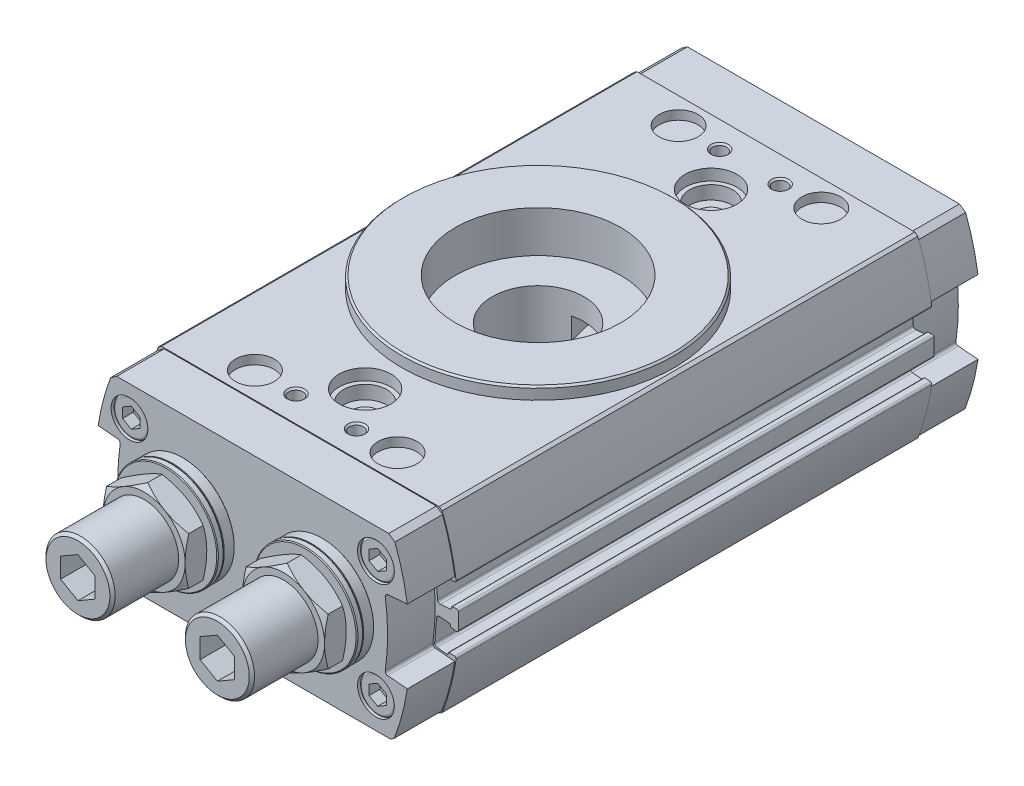
SolidWorks part; units mm, degrees
ref_plane "Front Plane" through (0, 0, 0) normal (0, 0, 1) x (1, 0, 0)
ref_plane "Top Plane" through (0, 0, 0) normal (0, 1, 0) x (1, 0, 0)
ref_plane "Right Plane" through (0, 0, 0) normal (1, 0, 0) x (0, 0, -1)
sketch "Sketch1" plane through (0, 0, 0) normal (0, 0, 1) x (1, 0, 0)
  line L0 (-32.8299, 0.5) -> (-32.1158, 0)
  line L1 (-32.1158, 0) -> (32.1158, 0)
  line L2 (32.1158, 0) -> (32.8299, 0.5)
  line L3 (32.8299, 40.9) -> (32.1158, 41.4)
  line L4 (32.1158, 41.4) -> (-32.1158, 41.4)
  line L5 (-32.1158, 41.4) -> (-32.8299, 40.9)
  arc A0 (-32.8299, 40.9) -> (-32.8299, 0.5) centre (19.4, 20.7) ccw
  arc A1 (32.8299, 0.5) -> (32.8299, 40.9) centre (-19.4, 20.7) ccw
extrude "Boss-Extrude1" add sketch "Sketch1" against normal blind 55 and the other way blind 55
sketch "Sketch2" plane through (0, 0, 0) normal (0, 0, 1) x (1, 0, 0)
  line L0 (31.6179, 12.9542) -> (33.9091, 12.7538)
  line L1 (34.2341, 13.0265) -> (34.2472, 13.1759)
  line L2 (34.4639, 13.3577) -> (35.6783, 13.2515)
  line L3 (36.0395, 12.7965) -> (41.6, 12.7965)
  line L4 (41.6, 12.7965) -> (41.6, 28.5837)
  line L5 (41.6, 28.5837) -> (36.0423, 28.5837)
  line L6 (35.6811, 28.1289) -> (34.6909, 28.0423)
  line L7 (34.4742, 28.2241) -> (34.4612, 28.3735)
  line L8 (34.1362, 28.6462) -> (31.8449, 28.4458)
  line L9 (31.2995, 27.7958) -> (31.7614, 22.5159)
  line L10 (32.4114, 21.9705) -> (34.7027, 22.171)
  line L11 (34.9754, 22.496) -> (34.9623, 22.6454)
  line L12 (35.1441, 22.8621) -> (36.1343, 22.9487)
  line L13 (36.1337, 18.4315) -> (34.9171, 18.5379)
  line L14 (34.7353, 18.7546) -> (34.7483, 18.904)
  line L15 (34.4756, 19.229) -> (32.1844, 19.4295)
  line L16 (31.5344, 18.8841) -> (31.0725, 13.6042)
  arc A0 (31.0725, 13.6042) -> (31.6179, 12.9542) centre (31.6702, 13.552) ccw
  arc A1 (33.9091, 12.7538) -> (34.2341, 13.0265) centre (33.9353, 13.0526) ccw
  arc A2 (34.2472, 13.1759) -> (34.4639, 13.3577) centre (34.4464, 13.1585) cw
  arc A3 (35.6783, 13.2515) -> (36.0395, 12.7965) centre (35.6435, 12.853) cw
  arc A4 (36.0423, 28.5837) -> (35.6811, 28.1289) centre (35.6463, 28.5274) cw
  arc A5 (34.6909, 28.0423) -> (34.4742, 28.2241) centre (34.6735, 28.2415) cw
  arc A6 (34.4612, 28.3735) -> (34.1362, 28.6462) centre (34.1623, 28.3474) ccw
  arc A7 (31.8449, 28.4458) -> (31.2995, 27.7958) centre (31.8972, 27.848) ccw
  arc A8 (31.7614, 22.5159) -> (32.4114, 21.9705) centre (32.3591, 22.5682) ccw
  arc A9 (34.7027, 22.171) -> (34.9754, 22.496) centre (34.6765, 22.4698) ccw
  arc A10 (34.9623, 22.6454) -> (35.1441, 22.8621) centre (35.1616, 22.6628) cw
  arc A11 (36.1343, 22.9487) -> (36.569, 22.5635) centre (36.1692, 22.5502) cw
  arc A12 (36.569, 22.5635) -> (36.5683, 18.8165) centre (-19.4, 20.7) cw
  arc A13 (36.5683, 18.8165) -> (36.1337, 18.4315) centre (36.1685, 18.83) cw
  arc A14 (34.9171, 18.5379) -> (34.7353, 18.7546) centre (34.9345, 18.7372) cw
  arc A15 (34.7483, 18.904) -> (34.4756, 19.229) centre (34.4495, 18.9302) ccw
  arc A16 (32.1844, 19.4295) -> (31.5344, 18.8841) centre (32.1321, 18.8318) ccw
extrude "Cut-Extrude1" cut sketch "Sketch2" along normal blind 55 and the other way blind 55
sketch "Sketch3" plane through (0, 0, 0) normal (0, 0, 1) x (1, 0, 0)
  line L0 (-41.6, 12.7965) -> (-36.0395, 12.7965)
  line L1 (-35.6783, 13.2515) -> (-34.4639, 13.3577)
  line L2 (-34.2472, 13.1759) -> (-34.2341, 13.0265)
  line L3 (-33.9091, 12.7538) -> (-31.6179, 12.9542)
  line L4 (-31.0725, 13.6042) -> (-31.5344, 18.8841)
  line L5 (-32.1844, 19.4295) -> (-34.4756, 19.229)
  line L6 (-34.7483, 18.904) -> (-34.7353, 18.7546)
  line L7 (-34.9171, 18.5379) -> (-36.1337, 18.4315)
  line L8 (-36.1343, 22.9487) -> (-35.1441, 22.8621)
  line L9 (-34.9623, 22.6454) -> (-34.9754, 22.496)
  line L10 (-34.7027, 22.171) -> (-32.4114, 21.9705)
  line L11 (-31.7614, 22.5159) -> (-31.2995, 27.7958)
  line L12 (-31.8449, 28.4458) -> (-34.1362, 28.6462)
  line L13 (-34.4612, 28.3735) -> (-34.4742, 28.2241)
  line L14 (-34.6909, 28.0423) -> (-35.6811, 28.1289)
  line L15 (-36.0423, 28.5837) -> (-41.6, 28.5837)
  line L16 (-41.6, 28.5837) -> (-41.6, 12.7965)
  arc A0 (-36.0395, 12.7965) -> (-35.6783, 13.2515) centre (-35.6435, 12.853) cw
  arc A1 (-34.4639, 13.3577) -> (-34.2472, 13.1759) centre (-34.4464, 13.1585) cw
  arc A2 (-34.2341, 13.0265) -> (-33.9091, 12.7538) centre (-33.9353, 13.0526) ccw
  arc A3 (-31.6179, 12.9542) -> (-31.0725, 13.6042) centre (-31.6702, 13.552) ccw
  arc A4 (-31.5344, 18.8841) -> (-32.1844, 19.4295) centre (-32.1321, 18.8318) ccw
  arc A5 (-34.4756, 19.229) -> (-34.7483, 18.904) centre (-34.4495, 18.9302) ccw
  arc A6 (-34.7353, 18.7546) -> (-34.9171, 18.5379) centre (-34.9345, 18.7372) cw
  arc A7 (-36.1337, 18.4315) -> (-36.5683, 18.8165) centre (-36.1685, 18.83) cw
  arc A8 (-36.5683, 18.8165) -> (-36.569, 22.5635) centre (19.4, 20.7) cw
  arc A9 (-36.569, 22.5635) -> (-36.1343, 22.9487) centre (-36.1692, 22.5502) cw
  arc A10 (-35.1441, 22.8621) -> (-34.9623, 22.6454) centre (-35.1616, 22.6628) cw
  arc A11 (-34.9754, 22.496) -> (-34.7027, 22.171) centre (-34.6765, 22.4698) ccw
  arc A12 (-32.4114, 21.9705) -> (-31.7614, 22.5159) centre (-32.3591, 22.5682) ccw
  arc A13 (-31.2995, 27.7958) -> (-31.8449, 28.4458) centre (-31.8972, 27.848) ccw
  arc A14 (-34.1362, 28.6462) -> (-34.4612, 28.3735) centre (-34.1623, 28.3474) ccw
  arc A15 (-34.4742, 28.2241) -> (-34.6909, 28.0423) centre (-34.6735, 28.2415) cw
  arc A16 (-35.6811, 28.1289) -> (-36.0423, 28.5837) centre (-35.6463, 28.5274) cw
extrude "Cut-Extrude2" cut sketch "Sketch3" along normal blind 55 and the other way blind 55
ref_plane "Plane1" through (0, 0, -55) normal (0, 0, 1) x (1, 0, 0)
sketch "Sketch4" plane through (0, 0, -55) normal (0, 0, 1) x (1, 0, 0)
  line L0 (-35.7512, 29.2) -> (-31.197, 28.8016)
  line L1 (-31.197, 12.5984) -> (-35.7512, 12.2)
  line L2 (-32.7449, 0.8) -> (-31.888, 0.2)
  line L3 (-31.888, 0.2) -> (31.888, 0.2)
  line L4 (31.888, 0.2) -> (32.7449, 0.8)
  line L5 (35.7512, 12.2) -> (31.197, 12.5984)
  line L6 (31.197, 28.8016) -> (35.7512, 29.2)
  line L7 (32.8953, 40.1997) -> (31.4668, 41.2)
  line L8 (31.4668, 41.2) -> (-31.4668, 41.2)
  line L9 (-31.4668, 41.2) -> (-32.8953, 40.1997)
  arc A0 (-31.197, 28.8016) -> (-30.6557, 28.1163) centre (-31.2493, 28.2038) cw
  arc A1 (-30.6557, 28.1163) -> (-30.6557, 13.2837) centre (19.6, 20.7) ccw
  arc A2 (-30.6557, 13.2837) -> (-31.197, 12.5984) centre (-31.2493, 13.1962) cw
  arc A3 (-35.7512, 12.2) -> (-32.7449, 0.8) centre (19.6, 20.7) ccw
  arc A4 (32.7449, 0.8) -> (35.7512, 12.2) centre (-19.6, 20.7) ccw
  arc A5 (31.197, 12.5984) -> (30.6557, 13.2837) centre (31.2493, 13.1962) cw
  arc A6 (30.6557, 13.2837) -> (30.6557, 28.1163) centre (-19.6, 20.7) ccw
  arc A7 (30.6557, 28.1163) -> (31.197, 28.8016) centre (31.2493, 28.2038) cw
  arc A8 (35.7512, 29.2) -> (32.8953, 40.1997) centre (-19.6, 20.7) ccw
  arc A9 (-32.8953, 40.1997) -> (-35.7512, 29.2) centre (19.6, 20.7) ccw
extrude "Boss-Extrude2" add sketch "Sketch4" against normal blind 11
ref_plane "Plane2" through (0, 0, 55) normal (0, 0, 1) x (1, 0, 0)
sketch "Sketch5" plane through (0, 0, 55) normal (0, 0, 1) x (1, 0, 0)
  line L0 (-35.7512, 29.2) -> (-31.197, 28.8016)
  line L1 (-31.197, 12.5984) -> (-35.7512, 12.2)
  line L2 (-32.7449, 0.8) -> (-31.888, 0.2)
  line L3 (-31.888, 0.2) -> (31.888, 0.2)
  line L4 (31.888, 0.2) -> (32.7449, 0.8)
  line L5 (35.7512, 12.2) -> (31.197, 12.5984)
  line L6 (31.197, 28.8016) -> (35.7512, 29.2)
  line L7 (32.8953, 40.1997) -> (31.4668, 41.2)
  line L8 (31.4668, 41.2) -> (-31.4668, 41.2)
  line L9 (-31.4668, 41.2) -> (-32.8953, 40.1997)
  arc A0 (-31.197, 28.8016) -> (-30.6557, 28.1163) centre (-31.2493, 28.2038) cw
  arc A1 (-30.6557, 28.1163) -> (-30.6557, 13.2837) centre (19.6, 20.7) ccw
  arc A2 (-30.6557, 13.2837) -> (-31.197, 12.5984) centre (-31.2493, 13.1962) cw
  arc A3 (-35.7512, 12.2) -> (-32.7449, 0.8) centre (19.6, 20.7) ccw
  arc A4 (32.7449, 0.8) -> (35.7512, 12.2) centre (-19.6, 20.7) ccw
  arc A5 (31.197, 12.5984) -> (30.6557, 13.2837) centre (31.2493, 13.1962) cw
  arc A6 (30.6557, 13.2837) -> (30.6557, 28.1163) centre (-19.6, 20.7) ccw
  arc A7 (30.6557, 28.1163) -> (31.197, 28.8016) centre (31.2493, 28.2038) cw
  arc A8 (35.7512, 29.2) -> (32.8953, 40.1997) centre (-19.6, 20.7) ccw
  arc A9 (-32.8953, 40.1997) -> (-35.7512, 29.2) centre (19.6, 20.7) ccw
extrude "Boss-Extrude3" add sketch "Sketch5" along normal blind 11
ref_plane "Plane3" through (0, 20.7, 0) normal (0, 1, 0) x (1, 0, 0)
sketch "Sketch6" plane through (0, 20.7, 0) normal (0, 1, 0) x (1, 0, 0)
  line L0 (10, 66) -> (12.5, 66)
  line L1 (12.5, 66) -> (12.067, 65.567)
  line L2 (12.067, 65.567) -> (12.067, 59)
  line L3 (12.067, 59) -> (10, 57.8066)
  line L4 (10, 57.8066) -> (10, 66)
  line L5 (10, 57.8066) -> (10, 66) construction
revolve "Cut-Revolve1" cut sketch "Sketch6" angle 360 about L5 reverse direction yes
cosmetic thread "Cosmetic Thread1" parameters "D1"=7, "D2"=5
sketch "Sketch7" plane through (0, 20.7, 0) normal (0, 1, 0) x (1, 0, 0)
  line L0 (-10, 66) -> (-7.5, 66)
  line L1 (-7.5, 66) -> (-7.933, 65.567)
  line L2 (-7.933, 65.567) -> (-7.933, 59)
  line L3 (-7.933, 59) -> (-10, 57.8066)
  line L4 (-10, 57.8066) -> (-10, 66)
  line L5 (-10, 57.8066) -> (-10, 66) construction
revolve "Cut-Revolve2" cut sketch "Sketch7" angle 360 about L5 reverse direction yes
cosmetic thread "Cosmetic Thread2" parameters "D1"=7, "D2"=5
ref_plane "Plane4" through (0, 20.7, 0) normal (0, 1, 0) x (1, 0, 0)
sketch "Sketch8" plane through (0, 0, 0) normal (0, 0, 1) x (1, 0, 0)
  line L0 (0, 44.2) -> (31.1, 44.2)
  line L1 (31.1, 44.2) -> (31.5, 43.8)
  line L2 (31.5, 43.8) -> (31.5, 41.4)
  line L3 (31.5, 41.4) -> (0, 41.4)
  line L4 (0, 41.4) -> (0, 44.2)
  line L5 (0, 41.4) -> (0, 44.2) construction
revolve "Revolve1" add sketch "Sketch8" angle 360 about L5 reverse direction yes
ref_plane "Plane5" through (0, 41.4, 0) normal (0, 1, 0) x (1, 0, 0)
ref_plane "Plane6" through (0, 0, 0) normal (0, 0, 1) x (1, 0, 0)
ref_plane "Plane7" through (0, 0, 0) normal (0, 0, 1) x (1, 0, 0)
ref_plane "Plane8" through (0, 41.1, 0) normal (0, 1, 0) x (1, 0, 0)
sketch "Sketch9" plane through (0, 0, 0) normal (0, 0, 1) x (1, 0, 0)
  line L0 (0, 44.7) -> (19.125, 44.7)
  line L1 (19.125, 44.7) -> (19.125, 34.6)
  line L2 (19.125, 34.6) -> (10.6, 34.6)
  line L3 (10.6, 34.6) -> (10.6, 9)
  line L4 (10.6, 9) -> (7.5, 9)
  line L5 (7.5, 9) -> (7.5, 1.4)
  line L6 (7.5, 1.4) -> (8.5, 1.4)
  line L7 (8.5, 1.4) -> (8.5, 0)
  line L8 (8.5, 0) -> (0, 0)
  line L9 (0, 0) -> (0, 44.7)
  line L10 (0, 0) -> (0, 44.7) construction
revolve "Cut-Revolve3" cut sketch "Sketch9" angle 360 about L10 reverse direction yes
sketch "Sketch10" plane through (0, 0, 0) normal (1, 0, 0) x (0, 0, -1)
  line L0 (40, 41.4) -> (46, 41.4)
  line L1 (46, 41.4) -> (46, 38.8)
  line L2 (46, 38.8) -> (45, 38.8)
  line L3 (45, 38.8) -> (45, 35.7)
  line L4 (45, 35.7) -> (43, 35.7)
  line L5 (43, 35.7) -> (42.4585, 35.1585)
  line L6 (42.4585, 35.1585) -> (42.4585, 3.1415)
  line L7 (42.4585, 3.1415) -> (43, 2.6)
  line L8 (43, 2.6) -> (46, 2.6)
  line L9 (46, 2.6) -> (46, 0)
  line L10 (46, 0) -> (40, 0)
  line L11 (40, 0) -> (40, 41.4)
  line L12 (40, 0) -> (40, 41.4) construction
revolve "Cut-Revolve4" cut sketch "Sketch10" angle 360 about L12 reverse direction yes
cosmetic thread "Cosmetic Thread3" parameters "D1"=33.1, "D2"=6
sketch "Sketch11" plane through (0, 0, 0) normal (1, 0, 0) x (0, 0, -1)
  line L0 (-40, 41.4) -> (-34, 41.4)
  line L1 (-34, 41.4) -> (-34, 38.8)
  line L2 (-34, 38.8) -> (-35, 38.8)
  line L3 (-35, 38.8) -> (-35, 35.7)
  line L4 (-35, 35.7) -> (-37, 35.7)
  line L5 (-37, 35.7) -> (-37.5415, 35.1585)
  line L6 (-37.5415, 35.1585) -> (-37.5415, 3.1415)
  line L7 (-37.5415, 3.1415) -> (-37, 2.6)
  line L8 (-37, 2.6) -> (-34, 2.6)
  line L9 (-34, 2.6) -> (-34, 0)
  line L10 (-34, 0) -> (-40, 0)
  line L11 (-40, 0) -> (-40, 41.4)
  line L12 (-40, 0) -> (-40, 41.4) construction
revolve "Cut-Revolve5" cut sketch "Sketch11" angle 360 about L12 reverse direction yes
cosmetic thread "Cosmetic Thread4" parameters "D1"=33.1, "D2"=6
ref_plane "Plane9" through (0, 0, 49) normal (0, 0, 1) x (1, 0, 0)
sketch "Sketch12" plane through (0, 0, 49) normal (0, 0, 1) x (1, 0, 0)
  line L0 (7, 41.4) -> (9, 41.4)
  line L1 (9, 41.4) -> (8.621, 41.021)
  line L2 (8.621, 41.021) -> (8.621, 32.9)
  line L3 (8.621, 32.9) -> (7, 31.9641)
  line L4 (7, 31.9641) -> (7, 41.4)
  line L5 (7, 31.9641) -> (7, 41.4) construction
revolve "Cut-Revolve6" cut sketch "Sketch12" angle 360 about L5 reverse direction yes
cosmetic thread "Cosmetic Thread5" parameters "D1"=7, "D2"=4
sketch "Sketch13" plane through (0, 0, 49) normal (0, 0, 1) x (1, 0, 0)
  line L0 (-7, 41.4) -> (-5, 41.4)
  line L1 (-5, 41.4) -> (-5.379, 41.021)
  line L2 (-5.379, 41.021) -> (-5.379, 32.9)
  line L3 (-5.379, 32.9) -> (-7, 31.9641)
  line L4 (-7, 31.9641) -> (-7, 41.4)
  line L5 (-7, 31.9641) -> (-7, 41.4) construction
revolve "Cut-Revolve7" cut sketch "Sketch13" angle 360 about L5 reverse direction yes
cosmetic thread "Cosmetic Thread6" parameters "D1"=7, "D2"=4
ref_plane "Plane10" through (0, 0, -49) normal (0, 0, 1) x (1, 0, 0)
sketch "Sketch14" plane through (0, 0, -49) normal (0, 0, 1) x (1, 0, 0)
  line L0 (7, 41.4) -> (9, 41.4)
  line L1 (9, 41.4) -> (8.621, 41.021)
  line L2 (8.621, 41.021) -> (8.621, 32.9)
  line L3 (8.621, 32.9) -> (7, 31.9641)
  line L4 (7, 31.9641) -> (7, 41.4)
  line L5 (7, 31.9641) -> (7, 41.4) construction
revolve "Cut-Revolve8" cut sketch "Sketch14" angle 360 about L5 reverse direction yes
cosmetic thread "Cosmetic Thread7" parameters "D1"=7, "D2"=4
sketch "Sketch15" plane through (0, 0, -49) normal (0, 0, 1) x (1, 0, 0)
  line L0 (-7, 41.4) -> (-5, 41.4)
  line L1 (-5, 41.4) -> (-5.379, 41.021)
  line L2 (-5.379, 41.021) -> (-5.379, 32.9)
  line L3 (-5.379, 32.9) -> (-7, 31.9641)
  line L4 (-7, 31.9641) -> (-7, 41.4)
  line L5 (-7, 31.9641) -> (-7, 41.4) construction
revolve "Cut-Revolve9" cut sketch "Sketch15" angle 360 about L5 reverse direction yes
cosmetic thread "Cosmetic Thread8" parameters "D1"=7, "D2"=4
ref_plane "Plane11" through (0, 0, 49) normal (0, 0, 1) x (1, 0, 0)
sketch "Sketch16" plane through (0, 0, 49) normal (0, 0, 1) x (1, 0, 0)
  line L0 (16.5, 41.4) -> (21, 41.4)
  line L1 (21, 41.4) -> (21, 39.3)
  line L2 (21, 39.3) -> (16.5, 39.3)
  line L3 (16.5, 39.3) -> (16.5, 41.4)
  line L4 (16.5, 39.3) -> (16.5, 41.4) construction
revolve "Cut-Revolve10" cut sketch "Sketch16" angle 360 about L4 reverse direction yes
sketch "Sketch17" plane through (0, 0, 49) normal (0, 0, 1) x (1, 0, 0)
  line L0 (-16.5, 41.4) -> (-12, 41.4)
  line L1 (-12, 41.4) -> (-12, 39.3)
  line L2 (-12, 39.3) -> (-16.5, 39.3)
  line L3 (-16.5, 39.3) -> (-16.5, 41.4)
  line L4 (-16.5, 39.3) -> (-16.5, 41.4) construction
revolve "Cut-Revolve11" cut sketch "Sketch17" angle 360 about L4 reverse direction yes
ref_plane "Plane12" through (0, 0, -49) normal (0, 0, 1) x (1, 0, 0)
sketch "Sketch18" plane through (0, 0, -49) normal (0, 0, 1) x (1, 0, 0)
  line L0 (16.5, 41.4) -> (21, 41.4)
  line L1 (21, 41.4) -> (21, 39.3)
  line L2 (21, 39.3) -> (16.5, 39.3)
  line L3 (16.5, 39.3) -> (16.5, 41.4)
  line L4 (16.5, 39.3) -> (16.5, 41.4) construction
revolve "Cut-Revolve12" cut sketch "Sketch18" angle 360 about L4 reverse direction yes
sketch "Sketch19" plane through (0, 0, -49) normal (0, 0, 1) x (1, 0, 0)
  line L0 (-16.5, 41.4) -> (-12, 41.4)
  line L1 (-12, 41.4) -> (-12, 39.3)
  line L2 (-12, 39.3) -> (-16.5, 39.3)
  line L3 (-16.5, 39.3) -> (-16.5, 41.4)
  line L4 (-16.5, 39.3) -> (-16.5, 41.4) construction
revolve "Cut-Revolve13" cut sketch "Sketch19" angle 360 about L4 reverse direction yes
ref_plane "Plane13" through (0, 7.2, 0) normal (0, 1, 0) x (1, 0, 0)
sketch "Sketch20" plane through (0, 7.2, 0) normal (0, 1, 0) x (1, 0, 0)
  line L0 (28.5, 66) -> (32.75, 66)
  line L1 (32.75, 66) -> (32.75, 65.1)
  line L2 (32.25, 65.6) -> (28.5, 65.6)
  line L3 (28.5, 65.6) -> (28.5, 66)
  line L4 (28.5, 65.6) -> (28.5, 66) construction
  arc A0 (32.75, 65.1) -> (32.25, 65.6) centre (32.25, 65.1) ccw
revolve "Cut-Revolve14" cut sketch "Sketch20" angle 360 about L4 reverse direction yes
sketch "Sketch21" plane through (0, 7.2, 0) normal (0, 1, 0) x (1, 0, 0)
  line L0 (-28.5, 66) -> (-24.25, 66)
  line L1 (-24.25, 66) -> (-24.25, 65.1)
  line L2 (-24.75, 65.6) -> (-28.5, 65.6)
  line L3 (-28.5, 65.6) -> (-28.5, 66)
  line L4 (-28.5, 65.6) -> (-28.5, 66) construction
  arc A0 (-24.25, 65.1) -> (-24.75, 65.6) centre (-24.75, 65.1) ccw
revolve "Cut-Revolve15" cut sketch "Sketch21" angle 360 about L4 reverse direction yes
sketch "Sketch22" plane through (0, 7.2, 0) normal (0, 1, 0) x (1, 0, 0)
  line L0 (28.5, -65.6) -> (32.25, -65.6)
  line L1 (32.75, -65.1) -> (32.75, -66)
  line L2 (32.75, -66) -> (28.5, -66)
  line L3 (28.5, -66) -> (28.5, -65.6)
  line L4 (28.5, -66) -> (28.5, -65.6) construction
  arc A0 (32.25, -65.6) -> (32.75, -65.1) centre (32.25, -65.1) ccw
revolve "Cut-Revolve16" cut sketch "Sketch22" angle 360 about L4 reverse direction yes
sketch "Sketch23" plane through (0, 7.2, 0) normal (0, 1, 0) x (1, 0, 0)
  line L0 (-28.5, -65.6) -> (-24.75, -65.6)
  line L1 (-24.25, -65.1) -> (-24.25, -66)
  line L2 (-24.25, -66) -> (-28.5, -66)
  line L3 (-28.5, -66) -> (-28.5, -65.6)
  line L4 (-28.5, -66) -> (-28.5, -65.6) construction
  arc A0 (-24.75, -65.6) -> (-24.25, -65.1) centre (-24.75, -65.1) ccw
revolve "Cut-Revolve17" cut sketch "Sketch23" angle 360 about L4 reverse direction yes
ref_plane "Plane14" through (0, 34.2, 0) normal (0, 1, 0) x (1, 0, 0)
sketch "Sketch24" plane through (0, 34.2, 0) normal (0, 1, 0) x (1, 0, 0)
  line L0 (28.5, 66) -> (32.75, 66)
  line L1 (32.75, 66) -> (32.75, 65.1)
  line L2 (32.25, 65.6) -> (28.5, 65.6)
  line L3 (28.5, 65.6) -> (28.5, 66)
  line L4 (28.5, 65.6) -> (28.5, 66) construction
  arc A0 (32.75, 65.1) -> (32.25, 65.6) centre (32.25, 65.1) ccw
revolve "Cut-Revolve18" cut sketch "Sketch24" angle 360 about L4 reverse direction yes
sketch "Sketch25" plane through (0, 34.2, 0) normal (0, 1, 0) x (1, 0, 0)
  line L0 (-28.5, 66) -> (-24.25, 66)
  line L1 (-24.25, 66) -> (-24.25, 65.1)
  line L2 (-24.75, 65.6) -> (-28.5, 65.6)
  line L3 (-28.5, 65.6) -> (-28.5, 66)
  line L4 (-28.5, 65.6) -> (-28.5, 66) construction
  arc A0 (-24.25, 65.1) -> (-24.75, 65.6) centre (-24.75, 65.1) ccw
revolve "Cut-Revolve19" cut sketch "Sketch25" angle 360 about L4 reverse direction yes
sketch "Sketch26" plane through (0, 34.2, 0) normal (0, 1, 0) x (1, 0, 0)
  line L0 (28.5, -65.6) -> (32.25, -65.6)
  line L1 (32.75, -65.1) -> (32.75, -66)
  line L2 (32.75, -66) -> (28.5, -66)
  line L3 (28.5, -66) -> (28.5, -65.6)
  line L4 (28.5, -66) -> (28.5, -65.6) construction
  arc A0 (32.25, -65.6) -> (32.75, -65.1) centre (32.25, -65.1) ccw
revolve "Cut-Revolve20" cut sketch "Sketch26" angle 360 about L4 reverse direction yes
sketch "Sketch27" plane through (0, 34.2, 0) normal (0, 1, 0) x (1, 0, 0)
  line L0 (-28.5, -65.6) -> (-24.75, -65.6)
  line L1 (-24.25, -65.1) -> (-24.25, -66)
  line L2 (-24.25, -66) -> (-28.5, -66)
  line L3 (-28.5, -66) -> (-28.5, -65.6)
  line L4 (-28.5, -66) -> (-28.5, -65.6) construction
  arc A0 (-24.75, -65.6) -> (-24.25, -65.1) centre (-24.75, -65.1) ccw
revolve "Cut-Revolve21" cut sketch "Sketch27" angle 360 about L4 reverse direction yes
ref_plane "Plane15" through (0, 0, 65.6) normal (0, 0, 1) x (1, 0, 0)
sketch "Sketch28" plane through (0, 0, 65.6) normal (0, 0, 1) x (1, 0, 0)
  line L0 (26.5, 33.0453) -> (28.5, 31.8906)
  line L1 (28.5, 31.8906) -> (30.5, 33.0453)
  line L2 (30.5, 33.0453) -> (30.5, 35.3547)
  line L3 (30.5, 35.3547) -> (28.5, 36.5094)
  line L4 (28.5, 36.5094) -> (26.5, 35.3547)
  line L5 (26.5, 35.3547) -> (26.5, 33.0453)
extrude "Cut-Extrude3" cut sketch "Sketch28" against normal blind 2.5
sketch "Sketch29" plane through (0, 0, 65.6) normal (0, 0, 1) x (1, 0, 0)
  line L0 (-30.5, 33.0453) -> (-28.5, 31.8906)
  line L1 (-28.5, 31.8906) -> (-26.5, 33.0453)
  line L2 (-26.5, 33.0453) -> (-26.5, 35.3547)
  line L3 (-26.5, 35.3547) -> (-28.5, 36.5094)
  line L4 (-28.5, 36.5094) -> (-30.5, 35.3547)
  line L5 (-30.5, 35.3547) -> (-30.5, 33.0453)
extrude "Cut-Extrude4" cut sketch "Sketch29" against normal blind 2.5
sketch "Sketch30" plane through (0, 0, 65.6) normal (0, 0, 1) x (1, 0, 0)
  line L0 (26.5, 6.0453) -> (28.5, 4.8906)
  line L1 (28.5, 4.8906) -> (30.5, 6.0453)
  line L2 (30.5, 6.0453) -> (30.5, 8.3547)
  line L3 (30.5, 8.3547) -> (28.5, 9.5094)
  line L4 (28.5, 9.5094) -> (26.5, 8.3547)
  line L5 (26.5, 8.3547) -> (26.5, 6.0453)
extrude "Cut-Extrude5" cut sketch "Sketch30" against normal blind 2.5
sketch "Sketch31" plane through (0, 0, 65.6) normal (0, 0, 1) x (1, 0, 0)
  line L0 (-30.5, 6.0453) -> (-28.5, 4.8906)
  line L1 (-28.5, 4.8906) -> (-26.5, 6.0453)
  line L2 (-26.5, 6.0453) -> (-26.5, 8.3547)
  line L3 (-26.5, 8.3547) -> (-28.5, 9.5094)
  line L4 (-28.5, 9.5094) -> (-30.5, 8.3547)
  line L5 (-30.5, 8.3547) -> (-30.5, 6.0453)
extrude "Cut-Extrude6" cut sketch "Sketch31" against normal blind 2.5
ref_plane "Plane16" through (0, 0, -65.6) normal (0, 0, 1) x (1, 0, 0)
sketch "Sketch32" plane through (0, 0, -65.6) normal (0, 0, 1) x (1, 0, 0)
  line L0 (26.5, 33.0453) -> (28.5, 31.8906)
  line L1 (28.5, 31.8906) -> (30.5, 33.0453)
  line L2 (30.5, 33.0453) -> (30.5, 35.3547)
  line L3 (30.5, 35.3547) -> (28.5, 36.5094)
  line L4 (28.5, 36.5094) -> (26.5, 35.3547)
  line L5 (26.5, 35.3547) -> (26.5, 33.0453)
extrude "Cut-Extrude7" cut sketch "Sketch32" along normal blind 2.5
sketch "Sketch33" plane through (0, 0, -65.6) normal (0, 0, 1) x (1, 0, 0)
  line L0 (-30.5, 33.0453) -> (-28.5, 31.8906)
  line L1 (-28.5, 31.8906) -> (-26.5, 33.0453)
  line L2 (-26.5, 33.0453) -> (-26.5, 35.3547)
  line L3 (-26.5, 35.3547) -> (-28.5, 36.5094)
  line L4 (-28.5, 36.5094) -> (-30.5, 35.3547)
  line L5 (-30.5, 35.3547) -> (-30.5, 33.0453)
extrude "Cut-Extrude8" cut sketch "Sketch33" along normal blind 2.5
sketch "Sketch34" plane through (0, 0, -65.6) normal (0, 0, 1) x (1, 0, 0)
  line L0 (26.5, 6.0453) -> (28.5, 4.8906)
  line L1 (28.5, 4.8906) -> (30.5, 6.0453)
  line L2 (30.5, 6.0453) -> (30.5, 8.3547)
  line L3 (30.5, 8.3547) -> (28.5, 9.5094)
  line L4 (28.5, 9.5094) -> (26.5, 8.3547)
  line L5 (26.5, 8.3547) -> (26.5, 6.0453)
extrude "Cut-Extrude9" cut sketch "Sketch34" along normal blind 2.5
sketch "Sketch35" plane through (0, 0, -65.6) normal (0, 0, 1) x (1, 0, 0)
  line L0 (-30.5, 6.0453) -> (-28.5, 4.8906)
  line L1 (-28.5, 4.8906) -> (-26.5, 6.0453)
  line L2 (-26.5, 6.0453) -> (-26.5, 8.3547)
  line L3 (-26.5, 8.3547) -> (-28.5, 9.5094)
  line L4 (-28.5, 9.5094) -> (-30.5, 8.3547)
  line L5 (-30.5, 8.3547) -> (-30.5, 6.0453)
extrude "Cut-Extrude10" cut sketch "Sketch35" along normal blind 2.5
sketch "Sketch36" plane through (0, 20.7, 0) normal (0, 1, 0) x (1, 0, 0)
  line L0 (16.125, -66) -> (27.975, -66)
  line L1 (27.975, -66) -> (28.075, -66.1)
  line L2 (28.075, -66.1) -> (28.075, -68.4)
  line L3 (28.075, -68.4) -> (27.975, -68.5)
  line L4 (27.975, -68.5) -> (16.125, -68.5)
  line L5 (16.125, -68.5) -> (16.125, -66)
  line L6 (16.125, -68.5) -> (16.125, -66) construction
revolve "Revolve2" add sketch "Sketch36" angle 360 about L6 reverse direction yes
sketch "Sketch37" plane through (0, 20.7, 0) normal (0, 1, 0) x (1, 0, 0)
  line L0 (-16.125, -66) -> (-4.275, -66)
  line L1 (-4.275, -66) -> (-4.175, -66.1)
  line L2 (-4.175, -66.1) -> (-4.175, -68.4)
  line L3 (-4.175, -68.4) -> (-4.275, -68.5)
  line L4 (-4.275, -68.5) -> (-16.125, -68.5)
  line L5 (-16.125, -68.5) -> (-16.125, -66)
  line L6 (-16.125, -68.5) -> (-16.125, -66) construction
revolve "Revolve3" add sketch "Sketch37" angle 360 about L6 reverse direction yes
sketch "Sketch38" plane through (0, 20.7, 0) normal (0, 1, 0) x (1, 0, 0)
  line L0 (16.125, -68.5) -> (27.925, -68.5)
  line L1 (27.925, -68.5) -> (28.125, -68.7)
  line L2 (28.125, -68.7) -> (28.125, -69.8)
  line L3 (28.125, -69.8) -> (27.925, -70)
  line L4 (27.925, -70) -> (16.125, -70)
  line L5 (16.125, -70) -> (16.125, -68.5)
  line L6 (16.125, -70) -> (16.125, -68.5) construction
revolve "Revolve4" add sketch "Sketch38" angle 360 about L6 reverse direction yes
sketch "Sketch39" plane through (0, 20.7, 0) normal (0, 1, 0) x (1, 0, 0)
  line L0 (-16.125, -68.5) -> (-4.3371, -68.5)
  line L1 (-4.3371, -68.5) -> (-4.125, -68.7121)
  line L2 (-4.125, -68.7121) -> (-4.125, -69.8232)
  line L3 (-4.125, -69.8232) -> (-4.3018, -70)
  line L4 (-4.3018, -70) -> (-16.125, -70)
  line L5 (-16.125, -70) -> (-16.125, -68.5)
  line L6 (-16.125, -70) -> (-16.125, -68.5) construction
revolve "Revolve5" add sketch "Sketch39" angle 360 about L6 reverse direction yes
ref_plane "Plane17" through (0, 0, 70) normal (0, 0, 1) x (1, 0, 0)
sketch "Sketch40" plane through (0, 0, 70) normal (0, 0, 1) x (1, 0, 0)
  line L0 (6.625, 15.2152) -> (16.125, 9.7303)
  line L1 (16.125, 9.7303) -> (25.625, 15.2152)
  line L2 (25.625, 15.2152) -> (25.625, 26.1848)
  line L3 (25.625, 26.1848) -> (16.125, 31.6697)
  line L4 (16.125, 31.6697) -> (6.625, 26.1848)
  line L5 (6.625, 26.1848) -> (6.625, 15.2152)
extrude "Boss-Extrude4" add sketch "Sketch40" along normal blind 5
sketch "Sketch41" plane through (0, 20.7, 0) normal (0, 1, 0) x (1, 0, 0)
  line L0 (25.625, -70) -> (28.075, -71.4145)
  line L1 (28.075, -71.4145) -> (28.075, -73.5855)
  line L2 (28.075, -73.5855) -> (25.625, -75)
  line L3 (25.625, -75) -> (29.075, -75)
  line L4 (29.075, -75) -> (29.075, -70)
  line L5 (29.075, -70) -> (25.625, -70)
  line L6 (16.125, -75) -> (16.125, -70) construction
revolve "Cut-Revolve22" cut sketch "Sketch41" angle 360 about L6 reverse direction yes
sketch "Sketch42" plane through (0, 0, 70) normal (0, 0, 1) x (1, 0, 0)
  line L0 (-25.625, 15.2152) -> (-16.125, 9.7303)
  line L1 (-16.125, 9.7303) -> (-6.625, 15.2152)
  line L2 (-6.625, 15.2152) -> (-6.625, 26.1848)
  line L3 (-6.625, 26.1848) -> (-16.125, 31.6697)
  line L4 (-16.125, 31.6697) -> (-25.625, 26.1848)
  line L5 (-25.625, 26.1848) -> (-25.625, 15.2152)
extrude "Boss-Extrude5" add sketch "Sketch42" along normal blind 5
sketch "Sketch43" plane through (0, 20.7, 0) normal (0, 1, 0) x (1, 0, 0)
  line L0 (-6.625, -75) -> (-3.175, -75)
  line L1 (-3.175, -75) -> (-3.175, -70)
  line L2 (-3.175, -70) -> (-6.625, -70)
  line L3 (-6.625, -70) -> (-4.175, -71.4145)
  line L4 (-4.175, -71.4145) -> (-4.175, -73.5855)
  line L5 (-4.175, -73.5855) -> (-6.625, -75)
  line L6 (-16.125, -75) -> (-16.125, -70) construction
revolve "Cut-Revolve23" cut sketch "Sketch43" angle 360 about L6 reverse direction yes
sketch "Sketch44" plane through (0, 20.7, 0) normal (0, 1, 0) x (1, 0, 0)
  line L0 (16.125, -75) -> (24.125, -75)
  line L1 (24.125, -75) -> (24.125, -89.6865)
  line L2 (24.125, -89.6865) -> (23.5115, -90.3)
  line L3 (23.5115, -90.3) -> (16.125, -90.3)
  line L4 (16.125, -90.3) -> (16.125, -75)
  line L5 (16.125, -90.3) -> (16.125, -75) construction
revolve "Revolve6" add sketch "Sketch44" angle 360 about L5 reverse direction yes
cosmetic thread "Cosmetic Thread9" parameters "D1"=15.3, "D2"=14.773
sketch "Sketch45" plane through (0, 20.7, 0) normal (0, 1, 0) x (1, 0, 0)
  line L0 (-16.125, -75) -> (-8.125, -75)
  line L1 (-8.125, -75) -> (-8.125, -89.6865)
  line L2 (-8.125, -89.6865) -> (-8.7385, -90.3)
  line L3 (-8.7385, -90.3) -> (-16.125, -90.3)
  line L4 (-16.125, -90.3) -> (-16.125, -75)
  line L5 (-16.125, -90.3) -> (-16.125, -75) construction
revolve "Revolve7" add sketch "Sketch45" angle 360 about L5 reverse direction yes
cosmetic thread "Cosmetic Thread10" parameters "D1"=15.3, "D2"=14.773
ref_plane "Plane18" through (0, 0, 129) normal (0, 0, 1) x (1, 0, 0)
ref_plane "Plane19" through (0, 0, 90.3) normal (0, 0, 1) x (1, 0, 0)
sketch "Sketch46" plane through (0, 0, 90.3) normal (0, 0, 1) x (1, 0, 0)
  line L0 (12.125, 18.3906) -> (16.125, 16.0812)
  line L1 (16.125, 16.0812) -> (20.125, 18.3906)
  line L2 (20.125, 18.3906) -> (20.125, 23.0094)
  line L3 (20.125, 23.0094) -> (16.125, 25.3188)
  line L4 (16.125, 25.3188) -> (12.125, 23.0094)
  line L5 (12.125, 23.0094) -> (12.125, 18.3906)
extrude "Cut-Extrude11" cut sketch "Sketch46" against normal blind 6
sketch "Sketch47" plane through (0, 0, 90.3) normal (0, 0, 1) x (1, 0, 0)
  line L0 (-20.125, 18.3906) -> (-16.125, 16.0812)
  line L1 (-16.125, 16.0812) -> (-12.125, 18.3906)
  line L2 (-12.125, 18.3906) -> (-12.125, 23.0094)
  line L3 (-12.125, 23.0094) -> (-16.125, 25.3188)
  line L4 (-16.125, 25.3188) -> (-20.125, 23.0094)
  line L5 (-20.125, 23.0094) -> (-20.125, 18.3906)
extrude "Cut-Extrude12" cut sketch "Sketch47" against normal blind 6
sketch "Sketch48" plane through (0, 0, 0) normal (1, 0, 0) x (0, 0, -1)
  line L0 (27.5, 0.4) -> (30.5, 0.4)
  line L1 (31, 0.9) -> (31, 4.4)
  line L2 (31, 4.4) -> (31.5, 4.4)
  line L3 (31.5, 4.4) -> (31.5, 2.1)
  line L4 (31.5, 2.1) -> (32, 2.1)
  line L5 (32, 2.1) -> (32, 0)
  line L6 (32, 0) -> (27.5, 0)
  line L7 (27.5, 0) -> (27.5, 0.4)
  line L8 (27.5, 0) -> (27.5, 0.4) construction
  arc A0 (30.5, 0.4) -> (31, 0.9) centre (30.5, 0.9) ccw
revolve "Cut-Revolve24" cut sketch "Sketch48" angle 360 about L8 reverse direction yes
sketch "Sketch49" plane through (0, 0, 0) normal (1, 0, 0) x (0, 0, -1)
  line L0 (-27.5, 0.4) -> (-24.5, 0.4)
  line L1 (-24, 0.9) -> (-24, 4.4)
  line L2 (-24, 4.4) -> (-23.5, 4.4)
  line L3 (-23.5, 4.4) -> (-23.5, 2.1)
  line L4 (-23.5, 2.1) -> (-23, 2.1)
  line L5 (-23, 2.1) -> (-23, 0)
  line L6 (-23, 0) -> (-27.5, 0)
  line L7 (-27.5, 0) -> (-27.5, 0.4)
  line L8 (-27.5, 0) -> (-27.5, 0.4) construction
  arc A0 (-24.5, 0.4) -> (-24, 0.9) centre (-24.5, 0.9) ccw
revolve "Cut-Revolve25" cut sketch "Sketch49" angle 360 about L8 reverse direction yes
ref_plane "Plane20" through (0, 0.4, 0) normal (0, 1, 0) x (1, 0, 0)
sketch "Sketch50" plane through (0, 0.4, 0) normal (0, 1, 0) x (1, 0, 0)
  line L0 (-1.5, 26.634) -> (0, 25.7679)
  line L1 (0, 25.7679) -> (1.5, 26.634)
  line L2 (1.5, 26.634) -> (1.5, 28.366)
  line L3 (1.5, 28.366) -> (0, 29.2321)
  line L4 (0, 29.2321) -> (-1.5, 28.366)
  line L5 (-1.5, 28.366) -> (-1.5, 26.634)
extrude "Cut-Extrude13" cut sketch "Sketch50" along normal blind 2
sketch "Sketch51" plane through (0, 0.4, 0) normal (0, 1, 0) x (1, 0, 0)
  line L0 (-1.5, -28.366) -> (0, -29.2321)
  line L1 (0, -29.2321) -> (1.5, -28.366)
  line L2 (1.5, -28.366) -> (1.5, -26.634)
  line L3 (1.5, -26.634) -> (0, -25.7679)
  line L4 (0, -25.7679) -> (-1.5, -26.634)
  line L5 (-1.5, -26.634) -> (-1.5, -28.366)
extrude "Cut-Extrude14" cut sketch "Sketch51" along normal blind 2
ref_plane "Plane21" through (0, 0, -55) normal (0, 0, 1) x (1, 0, 0)
ref_plane "Plane22" through (0, 20.7, 0) normal (0, 1, 0) x (1, 0, 0)
ref_plane "Plane23" through (0, 4.8, 0) normal (0, 1, 0) x (1, 0, 0)
ref_plane "Plane24" through (0, 30.7, 0) normal (0, 1, 0) x (1, 0, 0)
ref_plane "Plane25" through (0, 34.6, 0) normal (0, 1, 0) x (1, 0, 0)
ref_plane "Plane26" through (0, 30.6, 0) normal (0, 1, 0) x (1, 0, 0)
ref_plane "Plane27" through (0, 0, 0) normal (0.9703, 0, -0.2419) x (-0.2419, 0, -0.9703)
sketch "Sketch52" plane through (0, 0, 0) normal (0.9703, 0, -0.2419) x (-0.2419, 0, -0.9703)
  line L0 (0, 29.6) -> (17.125, 29.6)
  line L1 (17.125, 29.6) -> (17.125, 24.6)
  line L2 (17.125, 24.6) -> (0, 24.6)
  line L3 (0, 24.6) -> (0, 29.6)
  line L4 (0, 24.6) -> (0, 29.6) construction
revolve "Cut-Revolve26" cut sketch "Sketch52" angle 208 about L4 reverse direction yes
ref_plane "Plane28" through (0, 0, -66) normal (0, 0, 1) x (1, 0, 0)
ref_plane "Plane29" through (0, 0, 55) normal (0, 0, 1) x (1, 0, 0)
ref_plane "Plane30" through (0, 0, 66) normal (0, 0, 1) x (1, 0, 0)
ref_plane "Plane31" through (0, 0, 55) normal (0, 0, 1) x (1, 0, 0)
ref_plane "Plane32" through (0, 0, -55) normal (0, 0, 1) x (1, 0, 0)
ref_plane "Plane33" through (0, 0, -66) normal (0, 0, 1) x (1, 0, 0)
ref_plane "Plane34" through (0, 41.4, 0) normal (0, 1, 0) x (1, 0, 0)
ref_plane "Plane35" through (0, 0, 0) normal (1, 0, 0) x (0, 0, -1)
ref_plane "Plane36" through (0, 2.6, 0) normal (0, 1, 0) x (1, 0, 0)
ref_plane "ANBAU XY" through (0, 0, 0) normal (0, 1, 0) x (1, 0, 0)
ref_plane "ANBAU XZ" through (0, 0, 0) normal (0, 0, 1) x (1, 0, 0)
ref_plane "ANBAU YZ" through (0, 0, 0) normal (1, 0, 0) x (0, 0, -1)
ref_axis "ANBAU X" through (-80.9, 0, 0) along (1, 0, 0)
ref_axis "ANBAU Y" through (0, 0, 50) along (0, 0, -1)
ref_axis "ANBAU Z" through (0, 50, 0) along (0, -1, 0)
sketch3d "ANBAU"
  point P0 (0, 0, 0)
ref_plane "DASIQ11 XY" through (0, 0, 0) normal (0, 0, -1) x (-1, 0, 0)
ref_plane "DASIQ11 XZ" through (0, 41.8, 0) normal (0, 1, 0) x (1, 0, 0)
ref_plane "DASIQ11 YZ" through (0, 0, 0) normal (1, 0, 0) x (0, 0, -1)
ref_axis "DASIQ11 X" through (-80.9, 41.8, 0) along (1, 0, 0)
ref_axis "DASIQ11 Y" through (0, 50, 0) along (0, -1, 0)
ref_axis "DASIQ11 Z" through (0, 41.8, -80.9) along (0, 0, 1)
sketch3d "DASIQ11"
  point P0 (0, 41.8, 0)
ref_plane "FDT_QS1 XY" through (0, 0, -66) normal (0, 0, -1) x (-1, 0, 0)
ref_plane "FDT_QS1 XZ" through (0, 20.7, 0) normal (0, 1, 0) x (1, 0, 0)
ref_plane "FDT_QS1 YZ" through (10, 0, 0) normal (1, 0, 0) x (0, 0, -1)
ref_axis "FDT_QS1 X" through (-80.9, 20.7, -66) along (1, 0, 0)
ref_axis "FDT_QS1 Y" through (10, 50, -66) along (0, -1, 0)
ref_axis "FDT_QS1 Z" through (10, 20.7, -80.9) along (0, 0, 1)
sketch3d "FDT_QS1"
  point P0 (10, 20.7, -66)
ref_plane "FDT_QS2 XY" through (0, 0, -66) normal (0, 0, -1) x (-1, 0, 0)
ref_plane "FDT_QS2 XZ" through (0, 20.7, 0) normal (0, 1, 0) x (1, 0, 0)
ref_plane "FDT_QS2 YZ" through (-10, 0, 0) normal (1, 0, 0) x (0, 0, -1)
ref_axis "FDT_QS2 X" through (-80.9, 20.7, -66) along (1, 0, 0)
ref_axis "FDT_QS2 Y" through (-10, 50, -66) along (0, -1, 0)
ref_axis "FDT_QS2 Z" through (-10, 20.7, -80.9) along (0, 0, 1)
sketch3d "FDT_QS2"
  point P0 (-10, 20.7, -66)
ref_plane "FDT_SMX_LEFT_DOWN XY" through (-29.8806, -2.6142, 0) normal (-0.9962, -0.0872, 0) x (0, 0, 1)
ref_plane "FDT_SMX_LEFT_DOWN XZ" through (0, 0, 0) normal (0, 0, 1) x (1, 0, 0)
ref_plane "FDT_SMX_LEFT_DOWN YZ" through (-1.6499, 18.8584, 0) normal (-0.0872, 0.9962, 0) x (0.9962, 0.0872, 0)
ref_axis "FDT_SMX_LEFT_DOWN X" through (-25.5228, -52.4239, 0) along (-0.0872, 0.9962, 0)
ref_axis "FDT_SMX_LEFT_DOWN Y" through (-31.5305, 16.2442, 80.9) along (0, 0, -1)
ref_axis "FDT_SMX_LEFT_DOWN Z" through (-82.242, 11.8075, 0) along (0.9962, 0.0872, 0)
sketch3d "FDT_SMX_LEFT_DOWN"
  point P0 (-31.5305, 16.2442, 0)
ref_plane "FDT_SMX_LEFT_UP XY" through (-33.4751, 2.9287, 0) normal (-0.9962, 0.0872, 0) x (0, 0, 1)
ref_plane "FDT_SMX_LEFT_UP XZ" through (0, 0, 0) normal (0, 0, 1) x (1, 0, 0)
ref_plane "FDT_SMX_LEFT_UP YZ" through (1.9446, 22.2271, 0) normal (0.0872, 0.9962, 0) x (0.9962, -0.0872, 0)
ref_axis "FDT_SMX_LEFT_UP X" through (-37.8329, -46.881, 0) along (0.0872, 0.9962, 0)
ref_axis "FDT_SMX_LEFT_UP Y" through (-31.5305, 25.1558, 80.9) along (0, 0, -1)
ref_axis "FDT_SMX_LEFT_UP Z" through (-78.6475, 29.278, 0) along (0.9962, -0.0872, 0)
sketch3d "FDT_SMX_LEFT_UP"
  point P0 (-31.5305, 25.1558, 0)
ref_plane "FDT_SMX_RIGHT_DOWN XY" through (29.8806, -2.6142, 0) normal (0.9962, -0.0872, 0) x (0, 0, -1)
ref_plane "FDT_SMX_RIGHT_DOWN XZ" through (0, 0, 0) normal (0, 0, 1) x (1, 0, 0)
ref_plane "FDT_SMX_RIGHT_DOWN YZ" through (1.6499, 18.8584, 0) normal (-0.0872, -0.9962, 0) x (-0.9962, 0.0872, 0)
ref_axis "FDT_SMX_RIGHT_DOWN X" through (34.2383, 47.1955, 0) along (-0.0872, -0.9962, 0)
ref_axis "FDT_SMX_RIGHT_DOWN Y" through (31.5305, 16.2442, 80.9) along (0, 0, -1)
ref_axis "FDT_SMX_RIGHT_DOWN Z" through (82.242, 11.8075, 0) along (-0.9962, 0.0872, 0)
sketch3d "FDT_SMX_RIGHT_DOWN"
  point P0 (31.5305, 16.2442, 0)
ref_plane "FDT_SMX_RIGHT_UP XY" through (33.4751, 2.9287, 0) normal (0.9962, 0.0872, 0) x (0, 0, -1)
ref_plane "FDT_SMX_RIGHT_UP XZ" through (0, 0, 0) normal (0, 0, 1) x (1, 0, 0)
ref_plane "FDT_SMX_RIGHT_UP YZ" through (-1.9446, 22.2271, 0) normal (0.0872, -0.9962, 0) x (-0.9962, -0.0872, 0)
ref_axis "FDT_SMX_RIGHT_UP X" through (29.1173, 52.7384, 0) along (0.0872, -0.9962, 0)
ref_axis "FDT_SMX_RIGHT_UP Y" through (31.5305, 25.1558, 80.9) along (0, 0, -1)
ref_axis "FDT_SMX_RIGHT_UP Z" through (78.6475, 29.278, 0) along (-0.9962, -0.0872, 0)
sketch3d "FDT_SMX_RIGHT_UP"
  point P0 (31.5305, 25.1558, 0)
ref_plane "SLEEVE 1 XY" through (0, 2.6, 0) normal (0, 1, 0) x (1, 0, 0)
ref_plane "SLEEVE 1 XZ" through (0, 0, -40) normal (0, 0, 1) x (1, 0, 0)
ref_plane "SLEEVE 1 YZ" through (0, 0, 0) normal (1, 0, 0) x (0, 0, -1)
ref_axis "SLEEVE 1 X" through (-80.9, 2.6, -40) along (1, 0, 0)
ref_axis "SLEEVE 1 Y" through (0, 2.6, 50) along (0, 0, -1)
ref_axis "SLEEVE 1 Z" through (0, 50, -40) along (0, -1, 0)
sketch3d "SLEEVE 1"
  point P0 (0, 2.6, -40)
ref_plane "SLEEVE 2 XY" through (0, 2.6, 0) normal (0, 1, 0) x (1, 0, 0)
ref_plane "SLEEVE 2 XZ" through (0, 0, 40) normal (0, 0, 1) x (1, 0, 0)
ref_plane "SLEEVE 2 YZ" through (0, 0, 0) normal (1, 0, 0) x (0, 0, -1)
ref_axis "SLEEVE 2 X" through (-80.9, 2.6, 40) along (1, 0, 0)
ref_axis "SLEEVE 2 Y" through (0, 2.6, 50) along (0, 0, -1)
ref_axis "SLEEVE 2 Z" through (0, 50, 40) along (0, -1, 0)
sketch3d "SLEEVE 2"
  point P0 (0, 2.6, 40)
ref_plane "WELLEN XY" through (0, 34.6, 0) normal (0, -1, 0) x (-1, 0, 0)
ref_plane "WELLEN XZ" through (0, 0, 0) normal (0, 0, -1) x (-1, 0, 0)
ref_plane "WELLEN YZ" through (0, 0, 0) normal (1, 0, 0) x (0, 0, -1)
ref_axis "WELLEN X" through (-80.9, 34.6, 0) along (1, 0, 0)
ref_axis "WELLEN Y" through (0, 34.6, -50) along (0, 0, 1)
ref_axis "WELLEN Z" through (0, -50, 0) along (0, 1, 0)
sketch3d "WELLEN"
  point P0 (0, 34.6, 0)
other "Freeze***"
